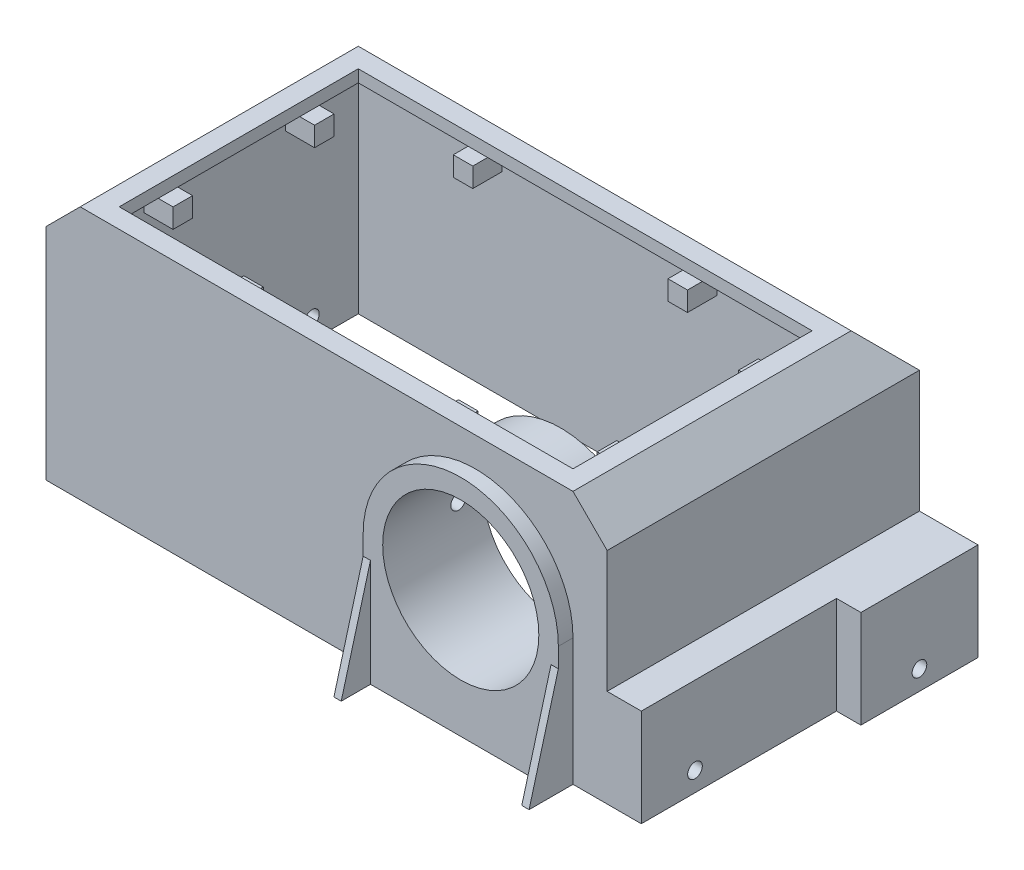
SolidWorks part; units mm, degrees
ref_plane "Front" through (0, 0, 0) normal (0, 0, 1) x (1, 0, 0)
ref_plane "Top" through (0, 0, 0) normal (0, 1, 0) x (1, 0, 0)
ref_plane "Right" through (0, 0, 0) normal (1, 0, 0) x (0, 0, -1)
sketch "Sketch1" plane through (0, 0, 0) normal (0, 0, 1) x (1, 0, 0)
  line L0 (63.5, -6) -> (51.5, -6)
  line L1 (-63.5, -26) -> (63.5, -26)
  line L2 (-63.5, -26) -> (-63.5, 26)
  line L3 (-63.5, 26) -> (63.5, 26)
  line L4 (63.5, -26) -> (63.5, 26)
  line L5 (-63.5, -26) -> (63.5, 26) construction
  line L6 (-63.5, 26) -> (63.5, -26) construction
  line L7 (51.5, -6) -> (51.5, 26)
  point P0 (0, 0)
  dimension "D1" = 52
  dimension "D2" = 127
  dimension "D3" = 12
  dimension "D4" = 20
extrude "Boss-Extrude1" add sketch "Sketch1" along normal blind 64 contours L0 L7 L3 L2 L1 L4 region at (-3.5498, -0.6174, 0)
sketch "Sketch2" plane through (0, 0, 64) normal (0, 0, 1) x (1, 0, 0)
  line L0 (-63.5, -26) -> (63.5, -26) construction
  line L1 (51.5, -6) -> (51.5, 26) construction
  circle A0 centre (24.5, 0) radius 16
  circle A1 centre (24.5, 0) radius 20
  dimension "D1" = 32
  dimension "D3" = 26
  dimension "D4" = 27
  dimension "D2" = 4
extrude "Boss-Extrude2" add sketch "Sketch2" along normal blind 3
chamfer "Chamfer1" distance 7 angle 45 3 edges at (-63.5, 26, 32) (-6, 26, 0) (51.5, 26, 32)
sketch "Sketch3" plane through (0, 0, 67) normal (0, 0, 1) x (1, 0, 0)
  line L0 (4.5, 0) -> (4.5, -26)
  line L1 (-63.5, -26) -> (63.5, -26) construction
  line L2 (6.5, -8.7178) -> (6.5, -26)
  line L3 (44.5, 0) -> (44.5, -26)
  line L4 (42.5, -8.7178) -> (42.5, -26)
  line L5 (6.5, 0) -> (6.5, -26) construction
  line L6 (42.5, 0) -> (42.5, -26) construction
  line L7 (4.5, 0) -> (4.5, -26) construction
  line L8 (4.5, -26) -> (44.5, -26)
  circle A0 centre (24.5, 0) radius 20 construction
  circle A1 centre (24.5, 0) radius 20 construction
  circle A2 centre (24.5, 0) radius 20
  circle M3 centre (24.5, 0) radius 20
  dimension "D1" = 2
  dimension "D2" = 2
extrude "Boss-Extrude3" add sketch "Sketch3" against normal up to next contours L0 L8 L2 M3 | L4 L8 L3 M3 | L2 L8 L4 M3 region at (5.4427, -15.8325, 67) region at (43.5573, -15.8325, 67) region at (24.5, -20.8713, 67)
sketch "Sketch4" plane through (0, 0, 67) normal (0, 0, 1) x (1, 0, 0)
  line L1 (4.5, -26) -> (6, -26)
  line L2 (4.5, -26) -> (4.5, -4)
  line L3 (4.5, -4) -> (6, -4)
  line L4 (6, -26) -> (6, -4)
  line L5 (4.5, -26) -> (6, -4) construction
  line L6 (4.5, -4) -> (6, -26) construction
  line L7 (44.5, -26) -> (43, -26)
  line L8 (44.5, -26) -> (44.5, -4)
  line L9 (44.5, -4) -> (43, -4)
  line L10 (43, -26) -> (43, -4)
  line L11 (44.5, -26) -> (43, -4) construction
  line L12 (44.5, -4) -> (43, -26) construction
  circle A0 centre (24.5, 0) radius 16 construction
  circle A1 centre (24.5, 0) radius 16
  point P7 (5.25, -15)
  point P13 (43.75, -15)
  line M2 (4.5, 0) -> (4.5, -26)
  line M3 (4.5, -26) -> (44.5, -26)
  line M4 (44.5, -26) -> (44.5, 0)
  dimension "D1" = 22
  dimension "D2" = 1.5
  dimension "D3" = 22
  dimension "D4" = 1.5
extrude "Boss-Extrude4" add sketch "Sketch4" along normal blind 6 contours L10 L9 M3 M4 | L4 L3 M3 M2 region at (5.25, -15, 67) region at (43.75, -15, 67)
sketch "Sketch5" plane through (4.5, 0, 0) normal (-1, 0, 0) x (0, 0, 1)
  line L0 (67, -4) -> (73, -26)
  line L1 (73, -26) -> (73, -4)
  line L2 (73, -4) -> (67, -4)
extrude "Cut-Extrude1" cut sketch "Sketch5" against normal through all
sketch "Sketch6" plane through (0, -6, 0) normal (0, 1, 0) x (1, 0, 0)
  line L1 (63.5, -64) -> (58.5, -64)
  line L2 (63.5, -64) -> (63.5, -24)
  line L3 (63.5, -24) -> (58.5, -24)
  line L4 (58.5, -64) -> (58.5, -24)
  line L5 (63.5, -64) -> (58.5, -24) construction
  line L6 (63.5, -24) -> (58.5, -64) construction
  point P4 (61, -44)
  dimension "D1" = 40
  dimension "D2" = 5
extrude "Cut-Extrude2" cut sketch "Sketch6" against normal through all
shell "Shell1" thickness 2.5 removed face at (22.3571, -26, 52.1429)
sketch "Sketch7" plane through (0, 0, 64) normal (0, 0, 1) x (1, 0, 0)
  circle A1 centre (24.5, 0) radius 16
  circle A2 centre (24.5, 0) radius 16
  dimension "D1" = 0
extrude "Cut-Extrude3" cut sketch "Sketch7" against normal up to next
sketch "Sketch8" plane through (0, 0, 61.5) normal (0, 0, -1) x (-1, 0, 0)
  circle A0 centre (-24.5, 0) radius 16 construction
  circle A1 centre (-24.5, 0) radius 16
  arc A2 (-42, -6) -> (-7, -6) centre (-24.5, 0) ccw construction
  arc A3 (-42, -6) -> (-7, -6) centre (-24.5, 0) ccw
  circle A4 centre (-24.5, 0) radius 18.5
  circle M2 centre (-24.5, 0) radius 16
  arc M14 (-42, -6) -> (-7, -6) centre (-24.5, 0) ccw
extrude "Boss-Extrude5" add sketch "Sketch8" along normal blind 15 contours A4 M14 M2 region at (27.4554, 17.7321, 61.5)
sketch "Sketch9" plane through (0, 26, 0) normal (0, 1, 0) x (1, 0, 0)
  line L14 (40.5, -60) -> (40.5, -11)
  line L15 (-52.5, -60) -> (40.5, -60)
  line L16 (-52.5, -11) -> (-52.5, -60)
  line L17 (40.5, -11) -> (-52.5, -11)
  line L18 (40.5, -60) -> (40.5, -11)
  line L19 (-52.5, -60) -> (40.5, -60)
  line L20 (-52.5, -11) -> (-52.5, -60)
  line L21 (40.5, -11) -> (-52.5, -11)
  dimension "D1" = 4
extrude "Cut-Extrude4" cut sketch "Sketch9" against normal up to next
sketch "Sketch10" plane through (0, 23.5, 0) normal (0, -1, 0) x (1, 0, 0)
  line L0 (-55.4645, 8.0355) -> (-55.4645, 61.5) construction
  line L1 (-55.4645, 52) -> (-49.4645, 52)
  line L2 (-55.4645, 52) -> (-55.4645, 48)
  line L3 (-55.4645, 48) -> (-49.4645, 48)
  line L4 (-49.4645, 52) -> (-49.4645, 48)
  line L5 (-55.4645, 52) -> (-49.4645, 48) construction
  line L6 (-55.4645, 48) -> (-49.4645, 52) construction
  line L7 (40.5, 60) -> (-52.5, 60) construction
  line L8 (-55.4645, 23) -> (-49.4645, 23)
  line L9 (-55.4645, 23) -> (-55.4645, 19)
  line L10 (-55.4645, 19) -> (-49.4645, 19)
  line L11 (-49.4645, 23) -> (-49.4645, 19)
  line L12 (-55.4645, 23) -> (-49.4645, 19) construction
  line L13 (-55.4645, 19) -> (-49.4645, 23) construction
  line L14 (-52.5, 11) -> (40.5, 11) construction
  line L15 (-6, 11) -> (-6, 19.8293) construction
  line L16 (43.4645, 19) -> (37.4645, 23) construction
  line L17 (43.4645, 23) -> (37.4645, 19) construction
  line L18 (43.4645, 48) -> (37.4645, 52) construction
  line L19 (43.4645, 52) -> (37.4645, 48) construction
  line L20 (37.4645, 23) -> (37.4645, 19)
  line L21 (43.4645, 19) -> (37.4645, 19)
  line L22 (43.4645, 23) -> (43.4645, 19)
  line L23 (43.4645, 23) -> (37.4645, 23)
  line L24 (37.4645, 52) -> (37.4645, 48)
  line L25 (43.4645, 48) -> (37.4645, 48)
  line L26 (43.4645, 52) -> (43.4645, 48)
  line L27 (43.4645, 52) -> (37.4645, 52)
  line L28 (43.4645, 8.0355) -> (-55.4645, 8.0355) construction
  line L29 (-30, 8.0355) -> (-26, 8.0355)
  line L30 (-30, 8.0355) -> (-30, 14.0355)
  line L31 (-30, 14.0355) -> (-26, 14.0355)
  line L32 (-26, 8.0355) -> (-26, 14.0355)
  line L33 (-30, 8.0355) -> (-26, 14.0355) construction
  line L34 (-30, 14.0355) -> (-26, 8.0355) construction
  line L35 (40.5, 35.5) -> (33.5247, 35.5) construction
  line L36 (14, 8.0355) -> (18, 8.0355)
  line L37 (14, 8.0355) -> (14, 14.0355)
  line L38 (14, 14.0355) -> (18, 14.0355)
  line L39 (18, 8.0355) -> (18, 14.0355)
  line L40 (14, 8.0355) -> (18, 14.0355) construction
  line L41 (14, 14.0355) -> (18, 8.0355) construction
  line L42 (40.5, 11) -> (40.5, 60) construction
  line L43 (14, 56.9645) -> (18, 62.9645) construction
  line L44 (14, 62.9645) -> (18, 56.9645) construction
  line L45 (-30, 56.9645) -> (-26, 62.9645) construction
  line L46 (-30, 62.9645) -> (-26, 56.9645) construction
  line L47 (-6, 60) -> (-6, 51.1707) construction
  line L48 (18, 62.9645) -> (18, 56.9645)
  line L49 (14, 56.9645) -> (18, 56.9645)
  line L50 (14, 62.9645) -> (14, 56.9645)
  line L51 (14, 62.9645) -> (18, 62.9645)
  line L52 (-26, 62.9645) -> (-26, 56.9645)
  line L53 (-30, 56.9645) -> (-26, 56.9645)
  line L54 (-30, 62.9645) -> (-30, 56.9645)
  line L55 (-30, 62.9645) -> (-26, 62.9645)
  point P4 (-52.4645, 50)
  point P11 (-52.4645, 21)
  point P26 (40.4645, 21)
  point P27 (40.4645, 50)
  point P32 (-28, 11.0355)
  point P39 (16, 11.0355)
  point P54 (16, 59.9645)
  point P55 (-28, 59.9645)
  dimension "D1" = 4
  dimension "D2" = 6
  dimension "D3" = 4
  dimension "D4" = 6
  dimension "D5" = 8
  dimension "D6" = 8
  dimension "D7" = 6
  dimension "D8" = 4
  dimension "D9" = 6
  dimension "D10" = 4
  dimension "D11" = 20
  dimension "D12" = 20
extrude "Boss-Extrude6" add sketch "Sketch10" along normal blind 4
sketch "Sketch11" plane through (-63.5, 0, 0) normal (-1, 0, 0) x (0, 0, 1)
  line L0 (0, -26) -> (0, 19) construction
  line L1 (64, -26) -> (64, 19) construction
  line L2 (0, -26) -> (26.355, -26) construction
  circle A0 centre (53, -22) radius 1.5
  circle A1 centre (12, -22) radius 1.5
  dimension "D1" = 3
  dimension "D2" = 3
  dimension "D3" = 12
  dimension "D4" = 11
  dimension "D5" = 4
extrude "Cut-Extrude5" cut sketch "Sketch11" against normal through all
sketch "Sketch12" plane through (0, 0, 0) normal (1, 0, 0) x (0, 0, -1)
  line L0 (-46.5, 0) -> (-51.5, 0) construction
  line L1 (-46.5, -18.5) -> (-46.5, 18.5) construction
  circle A0 centre (-51.5, 0) radius 1.55
  dimension "D2" = 3.1
  dimension "D1" = 5
extrude "Cut-Extrude6" cut sketch "Sketch12" along normal blind 44
